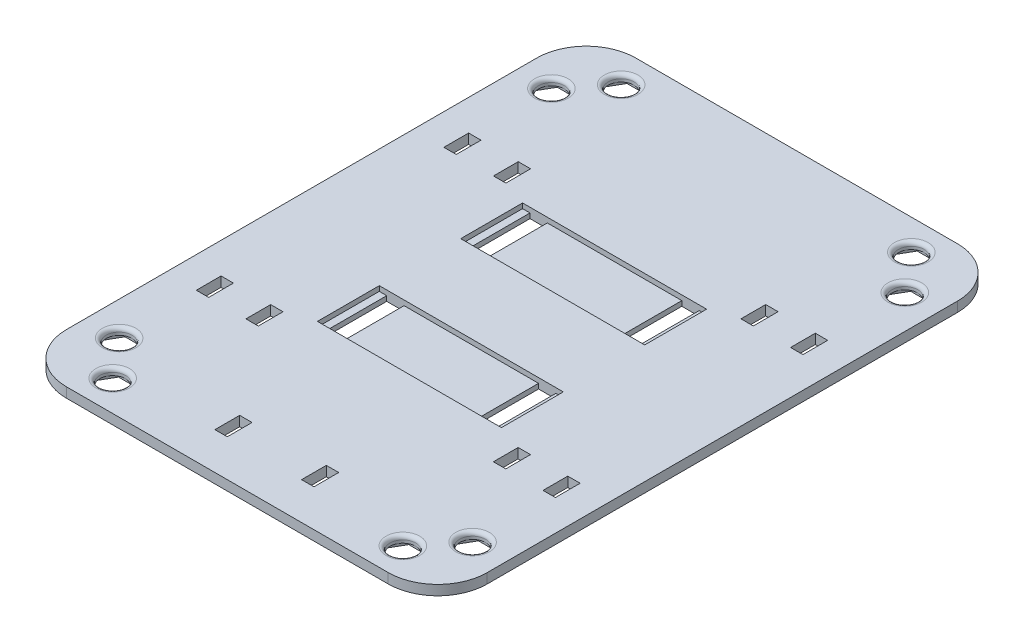
SolidWorks part; units mm, degrees
material "3-D Printed ABS"
ref_plane "Front Plane" through (0, 0, 0) normal (0, 0, 1) x (1, 0, 0)
ref_plane "Top Plane" through (0, 0, 0) normal (0, 1, 0) x (1, 0, 0)
ref_plane "Right Plane" through (0, 0, 0) normal (1, 0, 0) x (0, 0, -1)
sketch "Sketch1" plane through (0, 0, 0) normal (0, 1, 0) x (1, 0, 0)
  line L1 (-53.975, -73.025) -> (53.975, -73.025)
  line L2 (-53.975, -73.025) -> (-53.975, 73.025)
  line L3 (-53.975, 73.025) -> (53.975, 73.025)
  line L4 (53.975, -73.025) -> (53.975, 73.025)
  line L5 (-53.975, -73.025) -> (53.975, 73.025) construction
  line L6 (-53.975, 73.025) -> (53.975, -73.025) construction
  point P0 (0, 0)
  dimension "D1" = 107.95
  dimension "PlateY" = 146.05
extrude "Boss-Extrude1" add sketch "Sketch1" against normal blind 2.54
sketch "Sketch2" plane through (0, 0, 0) normal (0, 1, 0) x (1, 0, 0)
  line L0 (0, 0) -> (152.4, 0) construction
  line L1 (0, 0) -> (0, 152.4) construction
  line L4 (0, 0) -> (-53.975, 73.025) construction
  line L5 (0, 0) -> (-152.4, 0) construction
  line L6 (0, 0) -> (-152.4, 152.4) construction
  line L7 (-53.975, 73.025) -> (-53.975, -73.025) construction
  line L8 (53.975, 73.025) -> (-53.975, 73.025) construction
  line L9 (-152.4, 152.4) -> (-41.275, 60.325) construction
  line L10 (-41.275, 60.325) -> (0, 26.1257) construction
  line L11 (-30.7521, 73.025) -> (-53.975, 44.9974) construction
  circle A0 centre (-37.2189, 65.2108) radius 3.302
  circle A1 centre (45.3264, 55.4354) radius 3.302
  circle A2 centre (37.2189, 65.2108) radius 3.302
  circle A3 centre (-45.3264, -55.4354) radius 3.302
  circle A4 centre (-45.3264, 55.4354) radius 3.302
  circle A5 centre (-37.2189, -65.2108) radius 3.302
  circle A6 centre (37.2189, -65.2108) radius 3.302
  circle A7 centre (45.3264, -55.4354) radius 3.302
  point P12 (-41.275, 60.325)
  point P15 (-37.2189, 65.2108)
  dimension "D1" = 6.604
  dimension "D3" = 12.7
  dimension "D8" = 6.604
  dimension "D2" = 12.7
  dimension "D4" = 152.4
  dimension "D5" = 152.4
  dimension "D6" = 152.4
  dimension "D7" = 6.35
  dimension "D9" = 6.35
extrude "Cut-Extrude1" cut sketch "Sketch2" against normal through all
sketch "Sketch3" plane through (0, 0, 0) normal (0, 1, 0) x (1, 0, 0)
  line L0 (-53.975, 0) -> (53.975, 0) construction
  line L1 (-21.695, 26.3125) -> (-17.25, 26.3125)
  line L2 (-21.695, 26.3125) -> (-21.695, 10.4375)
  line L3 (-21.695, 10.4375) -> (-17.25, 10.4375)
  line L4 (-17.25, 26.3125) -> (-17.25, 10.4375)
  line L5 (17.25, 26.3125) -> (17.25, 10.4375)
  line L6 (21.695, 10.4375) -> (17.25, 10.4375)
  line L7 (21.695, 26.3125) -> (21.695, 10.4375)
  line L8 (21.695, 26.3125) -> (17.25, 26.3125)
  line L9 (-53.975, 73.025) -> (-53.975, -73.025) construction
  line L10 (53.975, -73.025) -> (53.975, 73.025) construction
  line L11 (0, -18.375) -> (0, 79.6704) construction
  line L12 (0, 18.375) -> (0, -79.6704) construction
  line L13 (21.695, -26.3125) -> (17.25, -26.3125)
  line L14 (21.695, -26.3125) -> (21.695, -10.4375)
  line L15 (21.695, -10.4375) -> (17.25, -10.4375)
  line L16 (17.25, -26.3125) -> (17.25, -10.4375)
  line L17 (-17.25, -26.3125) -> (-17.25, -10.4375)
  line L18 (-21.695, -10.4375) -> (-17.25, -10.4375)
  line L19 (-21.695, -26.3125) -> (-21.695, -10.4375)
  line L20 (-21.695, -26.3125) -> (-17.25, -26.3125)
  line L21 (-21.695, 18.375) -> (-33.6921, 18.375) construction
  line L22 (-53.975, -73.025) -> (53.975, -73.025) construction
  point P31 (0, -73.025)
  point P32 (-53.975, 0)
  dimension "D1" = 15.875
  dimension "D2" = 4.445
  dimension "D3" = 17.25
  dimension "D4" = 18.375
  dimension "D5" = 18.375
extrude "Cut-Extrude2" cut sketch "Sketch3" against normal through all
fillet "Fillet1" radius 12.7 4 edges at (53.975, -1.27, -73.025) (53.975, -1.27, 73.025) (-53.975, -1.27, 73.025) (-53.975, -1.27, -73.025)
sketch "Sketch4" plane through (0, 0, 0) normal (0, 1, 0) x (1, 0, 0)
  line L0 (0, 0) -> (80.9727, -80.9727) construction
  line L1 (0, 0) -> (-80.9727, -80.9727) construction
  line L2 (69.1118, -51.1513) -> (28.7006, -10.7401)
  line L3 (28.7006, -10.7401) -> (10.7401, -28.7006)
  line L4 (10.7401, -28.7006) -> (51.1513, -69.1118)
  line L5 (51.1513, -69.1118) -> (69.1118, -51.1513)
  line L6 (0, 0) -> (0, -118.7381) construction
  line L7 (0, 0) -> (-98.4177, 0) construction
  line L8 (-51.1513, -69.1118) -> (-69.1118, -51.1513)
  line L9 (-69.1118, -51.1513) -> (-28.7006, -10.7401)
  line L10 (-28.7006, -10.7401) -> (-10.7401, -28.7006)
  line L11 (-10.7401, -28.7006) -> (-51.1513, -69.1118)
  line L12 (-69.1118, 51.1513) -> (-28.7006, 10.7401)
  line L13 (-51.1513, 69.1118) -> (-69.1118, 51.1513)
  line L14 (-10.7401, 28.7006) -> (-51.1513, 69.1118)
  line L15 (-28.7006, 10.7401) -> (-10.7401, 28.7006)
  line L16 (51.1513, 69.1118) -> (69.1118, 51.1513)
  line L17 (69.1118, 51.1513) -> (28.7006, 10.7401)
  line L18 (28.7006, 10.7401) -> (10.7401, 28.7006)
  line L19 (10.7401, 28.7006) -> (51.1513, 69.1118)
  point P6 (19.7204, -19.7204)
  dimension "D1" = 25.4
  dimension "D2" = 57.15
  dimension "D3" = 45
extrude "Cut-Extrude3" [suppressed] cut sketch "Sketch4" against normal blind 1.5875
sketch "Sketch6" [suppressed] plane through (0, 0, 0) normal (0, 1, 0) x (1, 0, 0)
  line L0 (46.3377, -44.1074) -> (34.6634, -32.4331) construction
  line L1 (0, 0) -> (0, -117.7376) construction
  line L2 (0, 0) -> (-151.7285, 0) construction
  line L4 (28.1601, -10.1996) -> (10.1996, -28.1601) construction
  line L5 (50.6107, -68.5712) -> (68.5712, -50.6107) construction
  text T0 "ESC" font "Century Gothic" height in points 22
  dimension "D1" = 45
  dimension "D2" = 20.32
  dimension "D3" = 20.32
extrude "Cut-Extrude5" [suppressed] cut sketch "Sketch6" against normal blind 3.175
sketch "Sketch5" plane through (0, 0, 0) normal (0, 1, 0) x (1, 0, 0)
  line L0 (41.275, 73.025) -> (-41.275, 73.025) construction
  line L1 (14.2875, 15.875) -> (-14.2875, 15.875)
  line L2 (14.2875, 15.875) -> (14.2875, 66.675)
  line L3 (14.2875, 66.675) -> (-14.2875, 66.675)
  line L4 (-14.2875, 15.875) -> (-14.2875, 66.675)
  point P4 (0, 15.875)
  dimension "D1" = 50.8
  dimension "D2" = 28.575
  dimension "D3" = 6.35
extrude "Cut-Extrude4" [suppressed] cut sketch "Sketch5" against normal blind 1.5875
ref_axis "Axis1" through (0, 0.3175, 0) along (0, -1, 0)
pattern_circular "CirPattern1" [suppressed] count 4 over 360 about axis through (0, 0.3175, 0) along (0, -1, 0) of bodies 105
sketch "Sketch7" plane through (0, 0, 0) normal (0, 1, 0) x (1, 0, 0)
  line L0 (0, 0) -> (0, -54.962) construction
  line L1 (63.4018, -13.3522) -> (38.0018, -13.3522)
  line L2 (63.4018, -13.3522) -> (63.4018, 43.7978)
  line L3 (63.4018, 43.7978) -> (38.0018, 43.7978)
  line L4 (38.0018, -13.3522) -> (38.0018, 43.7978)
  line L5 (-38.0018, -13.3522) -> (-38.0018, 43.7978)
  line L6 (-63.4018, 43.7978) -> (-38.0018, 43.7978)
  line L7 (-63.4018, -13.3522) -> (-63.4018, 43.7978)
  line L8 (-63.4018, -13.3522) -> (-38.0018, -13.3522)
  line L9 (-41.275, -73.025) -> (41.275, -73.025) construction
  line L10 (38.5677, -40.64) -> (-18.5823, -40.64)
  line L11 (38.5677, -40.64) -> (38.5677, -66.04)
  line L12 (38.5677, -66.04) -> (-18.5823, -66.04)
  line L13 (-18.5823, -40.64) -> (-18.5823, -66.04)
  line L14 (38.5677, -40.64) -> (-18.5823, -66.04) construction
  line L15 (38.5677, -66.04) -> (-18.5823, -40.64) construction
  line L16 (19.844, -36.1003) -> (-37.306, -36.1003)
  line L17 (19.844, -36.1003) -> (19.844, -61.5003)
  line L18 (19.844, -61.5003) -> (-37.306, -61.5003)
  line L19 (-37.306, -36.1003) -> (-37.306, -61.5003)
  line L20 (19.844, -36.1003) -> (-37.306, -61.5003) construction
  line L21 (19.844, -61.5003) -> (-37.306, -36.1003) construction
  point P11 (9.9927, -53.34)
  point P18 (-8.731, -48.8003)
  dimension "D1" = 57.15
  dimension "D2" = 25.4
  dimension "D3" = 57.15
  dimension "D4" = 25.4
  dimension "D5" = 6.985
  dimension "D6" = 57.15
  dimension "D7" = 25.4
extrude "Cut-Extrude6" [suppressed] cut sketch "Sketch7" against normal blind 1.27
sketch "Sketch8" plane through (0, 0, 0) normal (0, 1, 0) x (1, 0, 0)
  line L7 (19.05, -31.75) -> (-19.05, -31.75)
  line L8 (19.05, -31.75) -> (19.05, 31.75)
  line L9 (19.05, 31.75) -> (-19.05, 31.75)
  line L10 (-19.05, -31.75) -> (-19.05, 31.75)
  point P0 (0, 0)
  dimension "D1" = 38.1
  dimension "D2" = 31.75
  dimension "D3" = 63.5
extrude "Boss-Extrude3" [suppressed] add sketch "Sketch8" along normal blind 2.54
sketch "Sketch11" plane through (0, 0, 0) normal (0, 1, 0) x (1, 0, 0)
  line L0 (-21.695, -26.3125) -> (-17.25, -26.3125) construction
  line L1 (23.6, -26.3125) -> (-23.6, -26.3125)
  line L2 (23.6, -26.3125) -> (23.6, -10.4375)
  line L3 (23.6, -10.4375) -> (-23.6, -10.4375)
  line L4 (-23.6, -26.3125) -> (-23.6, -10.4375)
  line L5 (21.695, -10.4375) -> (17.25, -10.4375) construction
  line L6 (21.695, -26.3125) -> (21.695, -10.4375) construction
  line L7 (-21.695, -10.4375) -> (-21.695, -26.3125) construction
  line L8 (0, 0) -> (90.9737, 0) construction
  line L9 (-23.6, 26.3125) -> (-23.6, 10.4375)
  line L10 (23.6, 10.4375) -> (-23.6, 10.4375)
  line L11 (23.6, 26.3125) -> (23.6, 10.4375)
  line L12 (23.6, 26.3125) -> (-23.6, 26.3125)
  dimension "D1" = 1.905
  dimension "D2" = 1.905
extrude "Cut-Extrude9" cut sketch "Sketch11" against normal mid plane 2.54
sketch "Sketch12" plane through (0, 0, 0) normal (0, 1, 0) x (1, 0, 0)
  line L1 (12.7, -34.5105) -> (-12.7, -34.5105)
  line L2 (12.7, -34.5105) -> (12.7, -18.375)
  line L3 (12.7, -18.375) -> (-12.7, -18.375)
  line L4 (-12.7, -34.5105) -> (-12.7, -18.375)
  line L6 (23.8125, 0) -> (-23.8125, 0) construction
  line L7 (-53.975, 60.325) -> (-53.975, -60.325) construction
  line L9 (-12.7, 34.5105) -> (-12.7, 18.375)
  line L10 (12.7, 18.375) -> (-12.7, 18.375)
  line L11 (12.7, 34.5105) -> (12.7, 18.375)
  line L12 (12.7, 34.5105) -> (-12.7, 34.5105)
  point P6 (-53.975, 0)
  dimension "D1" = 25.4
  dimension "D2" = 18.375
extrude "Cut-Extrude12" [suppressed] cut sketch "Sketch12" along normal through all
sketch "Sketch9" plane through (0, 0, 0) normal (0, 1, 0) x (1, 0, 0)
  line L1 (25.1579, -52.4084) -> (-25.6421, -52.4084)
  line L2 (25.1579, -52.4084) -> (25.1579, -1.6084)
  line L3 (25.1579, -1.6084) -> (-25.6421, -1.6084)
  line L4 (-25.6421, -52.4084) -> (-25.6421, -1.6084)
  line L5 (25.1579, -52.4084) -> (-25.6421, -1.6084) construction
  line L6 (25.1579, -1.6084) -> (-25.6421, -52.4084) construction
  point P0 (-0.2421, -27.0084)
  dimension "D1" = 50.8
  dimension "D2" = 50.8
sketch "Sketch13" plane through (0, 0, 0) normal (0, 1, 0) x (1, 0, 0)
  line L0 (0, 0) -> (0, -106.7514) construction
  line L1 (34.925, 3.175) -> (28.575, 3.175)
  line L2 (34.925, 3.175) -> (34.925, -3.175)
  line L3 (34.925, -3.175) -> (28.575, -3.175)
  line L4 (28.575, 3.175) -> (28.575, -3.175)
  line L5 (34.925, 3.175) -> (28.575, -3.175) construction
  line L6 (34.925, -3.175) -> (28.575, 3.175) construction
  line L7 (-34.925, -3.175) -> (-28.575, 3.175) construction
  line L8 (-34.925, 3.175) -> (-28.575, -3.175) construction
  line L9 (-28.575, 3.175) -> (-28.575, -3.175)
  line L10 (-34.925, -3.175) -> (-28.575, -3.175)
  line L11 (-34.925, 3.175) -> (-34.925, -3.175)
  line L12 (-34.925, 3.175) -> (-28.575, 3.175)
  point P0 (31.75, 0)
  point P12 (-31.75, 0)
  dimension "D1" = 6.35
  dimension "D2" = 28.575
  dimension "D3" = 0
extrude "Cut-Extrude13" [suppressed] cut sketch "Sketch13" against normal through all
fillet "Fillet2" radius 1.016 8 edges at (-37.2189, 0, -61.9088) (37.2189, 0, 68.5128) (45.3264, 0, 58.7374) (-37.2189, 0, 61.9088) (-45.3264, 0, 52.1334) (45.3264, 0, -58.7374) (37.2189, 0, -68.5128) (-45.3264, 0, -52.1334)
sketch "Sketch14" plane through (0, 0, 0) normal (0, 1, 0) x (1, 0, 0)
  line L0 (0, 76.698) -> (0, -76.698) construction
  line L1 (33.3248, -34.925) -> (30.1498, -34.925)
  line L2 (33.3248, -34.925) -> (33.3248, -28.575)
  line L3 (33.3248, -28.575) -> (30.1498, -28.575)
  line L4 (30.1498, -34.925) -> (30.1498, -28.575)
  line L5 (0, 0) -> (-92.4571, 0) construction
  line L6 (-30.1498, -34.925) -> (-30.1498, -28.575)
  line L7 (-33.3248, -28.575) -> (-30.1498, -28.575)
  line L8 (-33.3248, -34.925) -> (-33.3248, -28.575)
  line L9 (-33.3248, -34.925) -> (-30.1498, -34.925)
  line L10 (-33.3248, 34.925) -> (-30.1498, 34.925)
  line L11 (-33.3248, 34.925) -> (-33.3248, 28.575)
  line L12 (-33.3248, 28.575) -> (-30.1498, 28.575)
  line L13 (-30.1498, 34.925) -> (-30.1498, 28.575)
  line L14 (30.1498, 34.925) -> (30.1498, 28.575)
  line L15 (33.3248, 28.575) -> (30.1498, 28.575)
  line L16 (33.3248, 34.925) -> (33.3248, 28.575)
  line L17 (33.3248, 34.925) -> (30.1498, 34.925)
  line L18 (-41.275, -73.025) -> (41.275, -73.025) construction
  line L19 (-9.525, -63.5) -> (-9.525, -57.15)
  line L20 (12.7, -63.5) -> (9.525, -63.5)
  line L21 (12.7, -63.5) -> (12.7, -57.15)
  line L22 (12.7, -57.15) -> (9.525, -57.15)
  line L23 (38.1, -73.025) -> (38.1, 73.025) construction
  line L24 (41.275, 73.025) -> (-41.275, 73.025) construction
  line L25 (42.8752, 34.925) -> (46.0502, 34.925)
  line L26 (42.8752, 34.925) -> (42.8752, 28.575)
  line L27 (42.8752, 28.575) -> (46.0502, 28.575)
  line L28 (46.0502, 34.925) -> (46.0502, 28.575)
  line L29 (46.0502, -34.925) -> (46.0502, -28.575)
  line L30 (42.8752, -28.575) -> (46.0502, -28.575)
  line L31 (42.8752, -34.925) -> (42.8752, -28.575)
  line L32 (42.8752, -34.925) -> (46.0502, -34.925)
  line L33 (-46.0502, 34.925) -> (-46.0502, 28.575)
  line L34 (-42.8752, 28.575) -> (-46.0502, 28.575)
  line L35 (-42.8752, 34.925) -> (-42.8752, 28.575)
  line L36 (-42.8752, 34.925) -> (-46.0502, 34.925)
  line L37 (-42.8752, -34.925) -> (-46.0502, -34.925)
  line L38 (-42.8752, -34.925) -> (-42.8752, -28.575)
  line L39 (-42.8752, -28.575) -> (-46.0502, -28.575)
  line L40 (-46.0502, -34.925) -> (-46.0502, -28.575)
  line L41 (53.975, -50.8) -> (-53.975, -50.8) construction
  line L42 (53.975, -60.325) -> (53.975, 60.325) construction
  line L43 (-53.975, 60.325) -> (-53.975, -60.325) construction
  line L44 (0, -178.298) -> (0, -24.902) construction
  line L45 (9.525, -63.5) -> (9.525, -57.15)
  line L46 (-12.7, -57.15) -> (-9.525, -57.15)
  line L47 (-12.7, -63.5) -> (-12.7, -57.15)
  line L48 (-12.7, -63.5) -> (-9.525, -63.5)
  dimension "D2" = 3.175
  dimension "D3" = 6.35
  dimension "D4" = 28.575
  dimension "D5" = 3.175
  dimension "D6" = 6.35
  dimension "D7" = 9.525
  dimension "D8" = 9.525
  dimension "D9" = 38.1
  dimension "D10" = 22.225
  dimension "D11" = 30.1498
extrude "Cut-Extrude14" cut sketch "Sketch14" against normal through all
sketch "Sketch17" plane through (0, -2.54, 0) normal (0, -1, 0) x (1, 0, 0)
  line L0 (0, 0) -> (-152.4, 0) construction
  line L1 (0, 0) -> (0, -152.4) construction
  line L2 (0, -152.4) -> (-152.4, -152.4) construction
  line L3 (-152.4, -152.4) -> (-152.4, 0) construction
  line L4 (-152.4, -152.4) -> (0, 0) construction
  line L5 (41.275, -73.025) -> (-41.275, -73.025) construction
  line L6 (-53.975, -60.325) -> (-53.975, 60.325) construction
  line L7 (-152.4, -152.4) -> (-41.275, -60.325) construction
  line L8 (-41.275, -60.325) -> (0, -26.1257) construction
  line L9 (43.2734, -51.8794) -> (47.3795, -51.8794)
  line L10 (-41.2203, -55.4354) -> (-43.2734, -51.8794)
  line L11 (-43.2734, -51.8794) -> (-47.3795, -51.8794)
  line L12 (-47.3795, -51.8794) -> (-49.4325, -55.4354)
  line L13 (-49.4325, -55.4354) -> (-47.3795, -58.9914)
  line L14 (-47.3795, -58.9914) -> (-43.2734, -58.9914)
  line L15 (-43.2734, -58.9914) -> (-41.2203, -55.4354)
  line L16 (-33.1128, -65.2108) -> (-35.1659, -61.6548)
  line L17 (-35.1659, -61.6548) -> (-39.272, -61.6548)
  line L18 (-39.272, -61.6548) -> (-41.3251, -65.2108)
  line L19 (-41.3251, -65.2108) -> (-39.272, -68.7668)
  line L20 (-39.272, -68.7668) -> (-35.1659, -68.7668)
  line L21 (-35.1659, -68.7668) -> (-33.1128, -65.2108)
  line L22 (47.3795, -51.8794) -> (49.4325, -55.4354)
  line L23 (49.4325, -55.4354) -> (47.3795, -58.9914)
  line L24 (41.2203, -55.4354) -> (43.2734, -51.8794)
  line L25 (43.2734, -58.9914) -> (41.2203, -55.4354)
  line L26 (47.3795, -58.9914) -> (43.2734, -58.9914)
  line L27 (35.1659, -61.6548) -> (39.272, -61.6548)
  line L28 (33.1128, -65.2108) -> (35.1659, -61.6548)
  line L29 (39.272, -61.6548) -> (41.3251, -65.2108)
  line L30 (41.3251, -65.2108) -> (39.272, -68.7668)
  line L31 (35.1659, -68.7668) -> (33.1128, -65.2108)
  line L32 (39.272, -68.7668) -> (35.1659, -68.7668)
  line L33 (-41.2203, 55.4354) -> (-43.2734, 51.8794)
  line L34 (-43.2734, 51.8794) -> (-47.3795, 51.8794)
  line L35 (-47.3795, 51.8794) -> (-49.4325, 55.4354)
  line L36 (-49.4325, 55.4354) -> (-47.3795, 58.9914)
  line L37 (-47.3795, 58.9914) -> (-43.2734, 58.9914)
  line L38 (-43.2734, 58.9914) -> (-41.2203, 55.4354)
  line L39 (-33.1128, 65.2108) -> (-35.1659, 61.6548)
  line L40 (-35.1659, 61.6548) -> (-39.272, 61.6548)
  line L41 (-39.272, 61.6548) -> (-41.3251, 65.2108)
  line L42 (-41.3251, 65.2108) -> (-39.272, 68.7668)
  line L43 (-39.272, 68.7668) -> (-35.1659, 68.7668)
  line L44 (-35.1659, 68.7668) -> (-33.1128, 65.2108)
  line L45 (39.272, 68.7668) -> (35.1659, 68.7668)
  line L46 (35.1659, 68.7668) -> (33.1128, 65.2108)
  line L47 (41.3251, 65.2108) -> (39.272, 68.7668)
  line L48 (39.272, 61.6548) -> (41.3251, 65.2108)
  line L49 (33.1128, 65.2108) -> (35.1659, 61.6548)
  line L50 (35.1659, 61.6548) -> (39.272, 61.6548)
  line L51 (47.3795, 58.9914) -> (43.2734, 58.9914)
  line L52 (43.2734, 58.9914) -> (41.2203, 55.4354)
  line L53 (41.2203, 55.4354) -> (43.2734, 51.8794)
  line L54 (49.4325, 55.4354) -> (47.3795, 58.9914)
  line L55 (47.3795, 51.8794) -> (49.4325, 55.4354)
  line L56 (43.2734, 51.8794) -> (47.3795, 51.8794)
  circle A0 centre (-45.3264, -55.4354) radius 3.556 construction
  circle A1 centre (-37.2189, -65.2108) radius 3.556 construction
  point P0 (0, 0)
  point P6 (-41.275, -60.2488)
  dimension "D1" = 12.7762
  dimension "D2" = 12.7
  dimension "D3" = 7.112
  dimension "D4" = 7.112
extrude "Cut-Extrude15" cut sketch "Sketch17" against normal blind 0.7937
equation "\"Plate Dim Y\"= \"Plate Dim Y@Quad Assemb.SLDASM\""
equation "\"PlateY@Sketch1\" = \"Plate Dim Y\""
equation "\"D1@Sketch1\"= \"Plate Dim X\""
equation "\"D1@Boss-Extrude1\" = \"Plate Thickness\""
equation "\"Plate Dim X\"= \"Plate Dim X@Quad Assemb.SLDASM\""
equation "\"Plate Thickness\"= \"Plate Thickness@Quad Assemb.sldasm\""
equation "\"Batt X\"= \"Batt X@Quad Assemb.sldasm\""
equation "\"Batt Y\"= \"Batt Y@Quad Assemb.sldasm\""
equation "\"D3@Sketch3\"=\"Batt X\"/2"
equation "\"D4@Sketch3\"=\"Batt Y\"/4"
equation "\"D5@Sketch3\"=\"Batt Y\"*2/8"
equation "\"Dowell Width\"= \"Dowell Width@Quad Assemb.sldasm\""
equation "\"D1@Sketch2\"=\"Dowell Width\"+.01"
equation "\"D2@Sketch12\"=\"Batt Y\"/4"
equation "\"D7@Sketch2\"=\"Dowell Width\""
equation "\"D8@Sketch2\"=\"Dowell Width\" +0.01in"
equation "\"D9@Sketch2\"=\"Dowell Width\""
